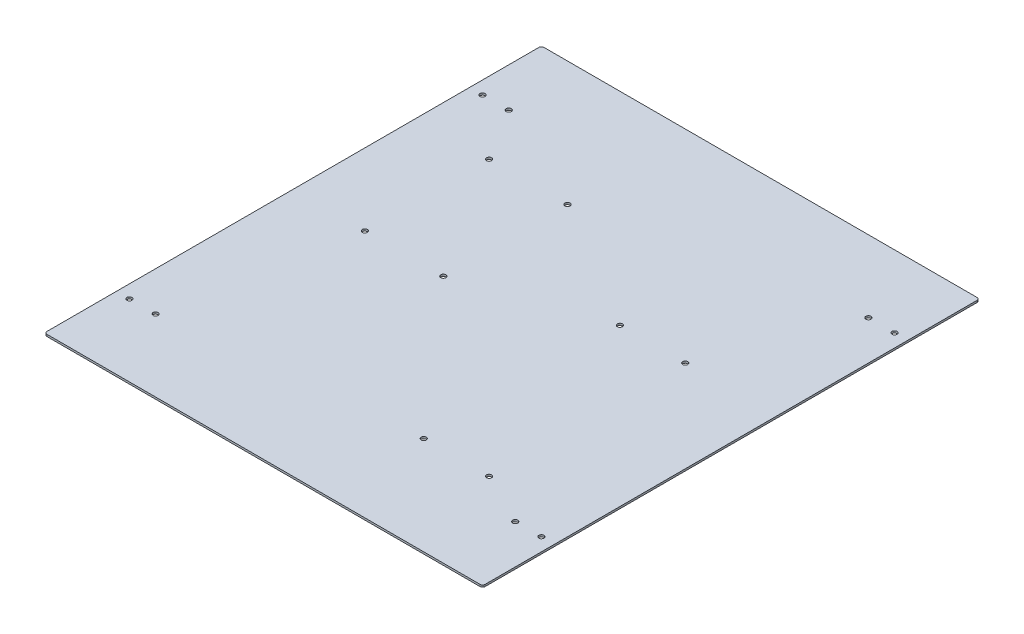
SolidWorks part; units mm, degrees
ref_plane "Front Plane" through (0, 0, 0) normal (0, 0, 1) x (1, 0, 0)
ref_plane "Top Plane" through (0, 0, 0) normal (0, 1, 0) x (1, 0, 0)
ref_plane "Right Plane" through (0, 0, 0) normal (1, 0, 0) x (0, 0, -1)
other "Center of Mass"
sketch "Sketch1" plane through (0, 0, 0) normal (0, 1, 0) x (1, 0, 0)
  line L1 (-167.5, -190) -> (167.5, -190)
  line L2 (-167.5, -190) -> (-167.5, 190)
  line L3 (-167.5, 190) -> (167.5, 190)
  line L4 (167.5, -190) -> (167.5, 190)
  line L5 (-167.5, -190) -> (167.5, 190) construction
  line L6 (-167.5, 190) -> (167.5, -190) construction
  point P0 (0, 0)
  dimension "D1" = 335
  dimension "D2" = 380
extrude "Boss-Extrude1" add sketch "Sketch1" along normal blind 1.5
sketch "Sketch6" plane through (0, 1.5, 0) normal (0, 1, 0) x (1, 0, 0)
  line L0 (167.5, -190) -> (167.5, 190) construction
  line L5 (-167.5, -190) -> (167.5, -190) construction
  circle A0 centre (97.5, 35) radius 1.95
  circle A1 centre (47.5, 35) radius 1.95
  circle A2 centre (97.5, -115) radius 1.95
  circle A3 centre (47.5, -115) radius 1.95
  dimension "D1" = 50
  dimension "D2" = 150
  dimension "D3" = 70
  dimension "D4" = 75
sketch "Sketch7" plane through (0, 1.5, 0) normal (0, 1, 0) x (1, 0, 0)
  line L0 (-167.5, 190) -> (-167.5, -190) construction
  line L1 (167.5, 190) -> (-167.5, 190) construction
  circle A0 centre (-112.5, 95) radius 1.95
  circle A1 centre (-52.5, 95) radius 1.95
  circle A2 centre (-52.5, 0) radius 1.95
  circle A3 centre (-112.5, 0) radius 1.95
  dimension "D1" = 95
  dimension "D3" = 55
  dimension "D2" = 60
  dimension "D4" = 95
sketch "Sketch12" plane through (0, 0, 0) normal (0, -1, 0) x (-1, 0, 0)
  line L0 (-167.5, 190) -> (167.5, 190) construction
  line L1 (167.5, -190) -> (-167.5, -190) construction
  line L2 (167.5, 190) -> (167.5, -190) construction
  line L3 (-167.5, -190) -> (-167.5, 190) construction
  circle A0 centre (-137.5, -135) radius 1.95
  circle A1 centre (-157.5, 135) radius 1.95
  circle A5 centre (-157.5, -135) radius 1.95
  circle A6 centre (-137.5, 135) radius 1.95
  circle A7 centre (157.5, -135) radius 1.95
  circle A9 centre (137.5, 135) radius 1.95
  circle A10 centre (157.5, 135) radius 1.95
  circle A11 centre (137.5, -135) radius 1.95
  point P2 (0, 0)
  point P3 (0, 0)
  point P6 (0, 0)
  point P7 (0, 0)
  point P12 (0, 0)
  point P13 (0, 0)
  point P22 (0, 0)
  dimension "D1" = 55
  dimension "D2" = 55
  dimension "D3" = 55
  dimension "D5" = 10
  dimension "D6" = 20
  dimension "D7" = 20
  dimension "D4" = 55
  dimension "D8" = 10
extrude "Cut-Extrude3" cut sketch "Sketch12" against normal blind 50.8
extrude "Cut-Extrude4" cut sketch "Sketch6" against normal blind 50.8
extrude "Cut-Extrude5" cut sketch "Sketch7" against normal blind 50.8
fillet "Fillet1" radius 2 4 edges at (167.5, 0.75, -190) (167.5, 0.75, 190) (-167.5, 0.75, 190) (-167.5, 0.75, -190)
